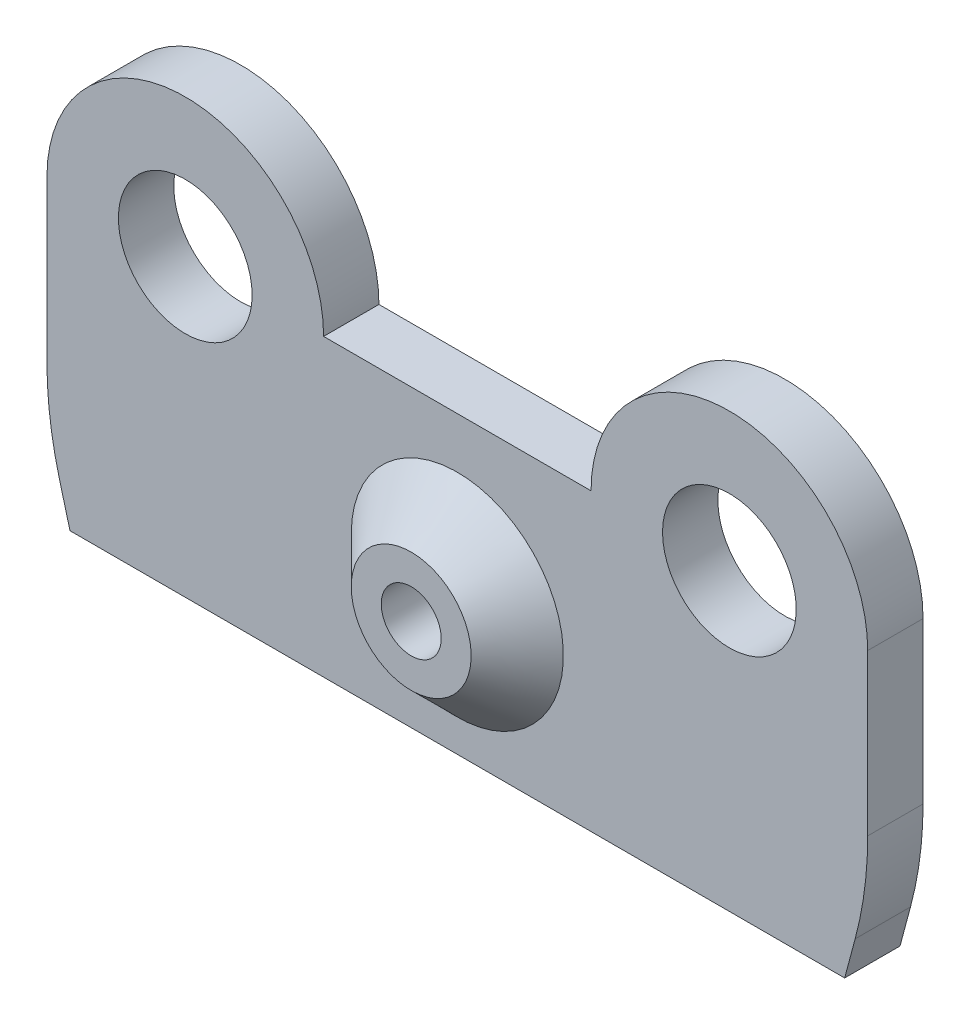
SolidWorks part; units mm, degrees
ref_plane "Front Plane" through (0, 0, 0) normal (0, 0, 1) x (1, 0, 0)
ref_plane "Top Plane" through (0, 0, 0) normal (0, 1, 0) x (1, 0, 0)
ref_plane "Right Plane" through (0, 0, 0) normal (1, 0, 0) x (0, 0, -1)
sketch "Sketch1" plane through (0, 0, 0) normal (0, 0, 1) x (1, 0, 0)
  line L0 (-29.5, 0) -> (0, 0) construction
  line L1 (0, 0) -> (0, 28.6284) construction
  line L2 (-44.5, 0) -> (-44.5, -32)
  line L3 (-44.5, -32) -> (44.5, -32)
  line L4 (44.5, -32) -> (44.5, 0)
  line L5 (-14.5, 0) -> (14.5, 0)
  circle A0 centre (-29.5, 0) radius 7.25
  arc A1 (-14.5, 0) -> (-44.5, 0) centre (-29.5, 0) ccw
  arc A2 (14.5, 0) -> (44.5, 0) centre (29.5, 0) cw
  circle A3 centre (29.5, 0) radius 7.25
  circle A4 centre (0, -17) radius 3.25
  dimension "D1" = 14.5
  dimension "D2" = 30
  dimension "D5" = 6.5
  dimension "D3" = 29.5
  dimension "D4" = 32
  dimension "D6" = 17
extrude "Boss-Extrude1" add sketch "Sketch1" along normal blind 6
sketch "Sketch2" plane through (0, 0, 6) normal (0, 0, 1) x (1, 0, 0)
  circle A0 centre (0, -17) radius 6.5
  circle A1 centre (0, -17) radius 3.25
  dimension "D1" = 13
  dimension "D2" = 6.5
extrude "Boss-Extrude2" add sketch "Sketch2" along normal blind 5
chamfer "Chamfer1" distance 5 angle 45 1 edges at (-6.5, -17, 6)
chamfer "Chamfer2" distance 2.5 angle 75 1 edges at (-44.5, -32, 3) first distance on face at (0, -32, 3)
fillet "Fillet1" radius 40 1 edges at (-44.5, -22.6699, 3)
chamfer "Chamfer3" distance 2.5 angle 75 1 edges at (44.5, -32, 3) first distance on face at (1.25, -32, 3)
fillet "Fillet2" radius 40 1 edges at (44.5, -22.6699, 3)
